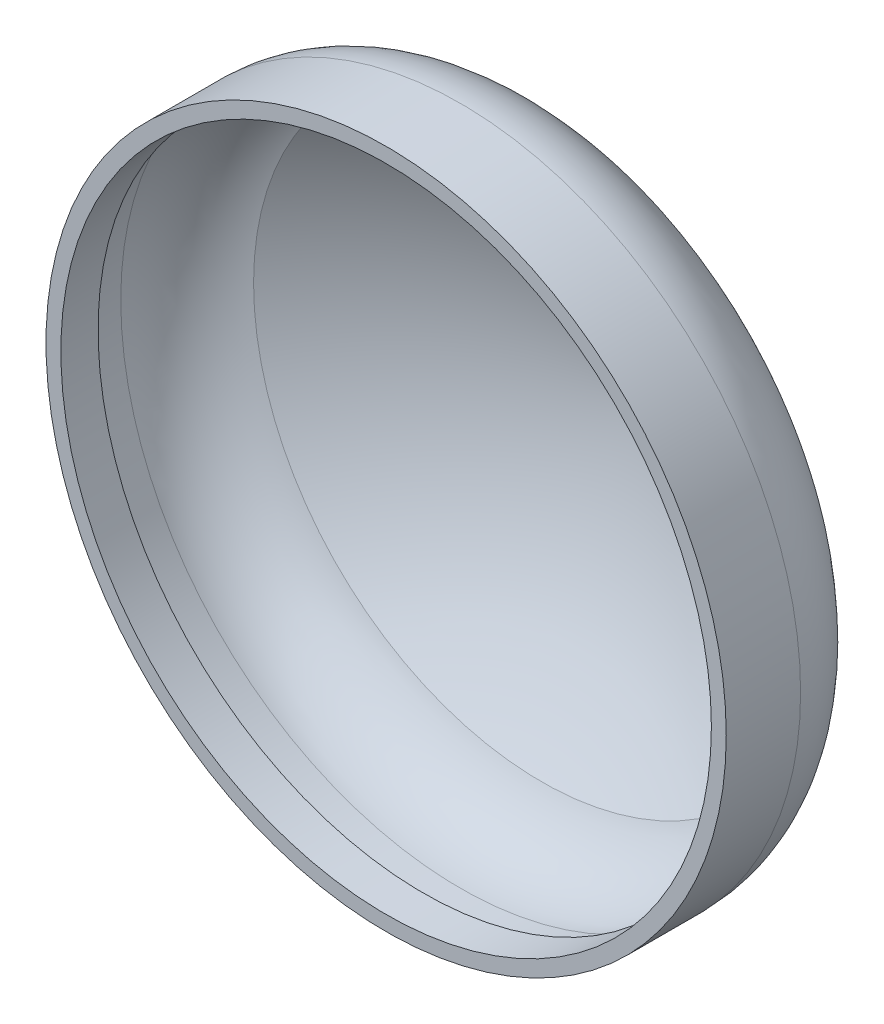
SolidWorks part; units mm, degrees
material "Steel Stainless 302"
ref_plane "Front Plane" through (0, 0, 0) normal (0, 0, 1) x (1, 0, 0)
ref_plane "Top Plane" through (0, 0, 0) normal (0, 1, 0) x (1, 0, 0)
ref_plane "Right Plane" through (0, 0, 0) normal (1, 0, 0) x (0, 0, -1)
sketch "Sketch1" plane through (0, 0, 0) normal (0, 0, 1) x (1, 0, 0)
  circle A0 centre (0, 0) radius 444.5
  circle A1 centre (0, 0) radius 464.82
  dimension "D1" = 889
  dimension "D2" = 929.64
extrude "Boss-Extrude1" add sketch "Sketch1" along normal blind 50.8
sketch "Sketch2" plane through (0, 0, 0) normal (1, 0, 0) x (0, 0, -1)
  line L0 (0, 0) -> (304.8, 0) construction
  line L3 (0, 0) -> (304.8, 0) construction
  line L4 (0, 0) -> (304.8, 0)
  line L5 (0, 0) -> (0, -464.82)
  line L6 (0, -464.82) -> (50.8, -464.82)
  arc A2 (50.8, -464.82) -> (162.1136, -393.8873) centre (50.8, -342.0123) ccw
  arc A3 (162.1136, -393.8873) -> (304.8, 0) centre (-446.8956, 49.5153) ccw
  dimension "D1" = 304.8
  dimension "D2" = 50.8
revolve "Revolve1" add sketch "Sketch2" angle 360 about L0
shell "Shell5" thickness 0.5588 removed face at (444.5, 0, 0)
